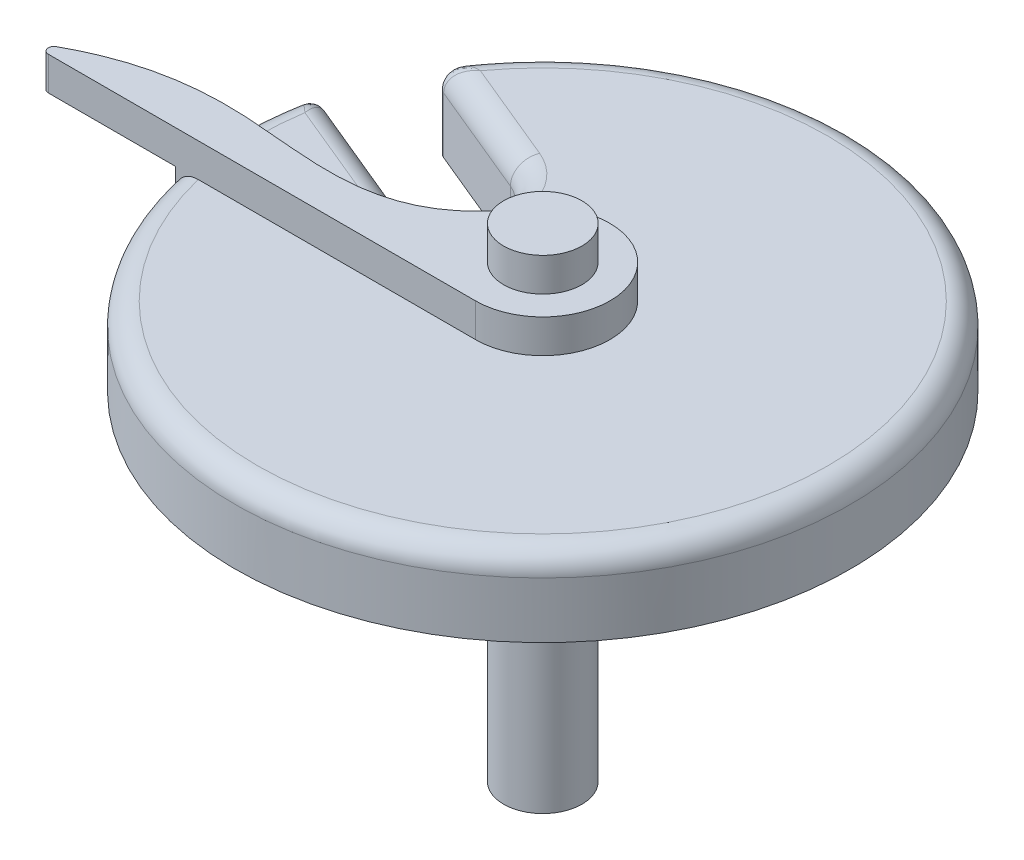
SolidWorks part; units mm, degrees
ref_plane "Front Plane" through (0, 0, 0) normal (0, 0, 1) x (1, 0, 0)
ref_plane "Top Plane" through (0, 0, 0) normal (0, 1, 0) x (1, 0, 0)
ref_plane "Right Plane" through (0, 0, 0) normal (1, 0, 0) x (0, 0, -1)
sketch "Sketch1" plane through (0, 0, 0) normal (0, 1, 0) x (1, 0, 0)
  circle A0 centre (0, 0) radius 27.5
  dimension "D1" = 55
extrude "Boss-Extrude1" add sketch "Sketch1" along normal blind 7
sketch "Sketch2" plane through (0, 7, 0) normal (0, 1, 0) x (1, 0, 0)
  line L0 (0, -6) -> (-40, -6)
  arc A0 (0, -6) -> (-5, 3.3166) centre (0, 0) ccw
  spline S0 degree 3 poles (-5, 3.3166) (-10.2937, -4.6639) (-24.0961, -0.4347) (-35.0297, -2.8344) (-40, -6) knots 0 0 0 0 0.566042 1 1 1 1
  point P7 (0, 0)
  point P8 (0, 0)
  point P9 (-25, -2.3178)
  point P11 (-0.086, 0.4917)
  dimension "D1" = 12
  dimension "D5" = 28.73
  dimension "D2" = 40
  dimension "D3" = 25
  dimension "D4" = 2
  dimension "D6" = 5
extrude "Boss-Extrude2" add sketch "Sketch2" along normal blind 3
fillet "Fillet1" radius 0.5 1 edges at (-40, 8.5, 6)
sketch "Sketch3" plane through (0, 10, 0) normal (0, 1, 0) x (1, 0, 0)
  circle A0 centre (0, 0) radius 3.5
  dimension "D1" = 7
extrude "Boss-Extrude3" add sketch "Sketch3" along normal blind 3 and the other way blind 40.2
sketch "Sketch4" plane through (0, 7, 0) normal (0, 1, 0) x (1, 0, 0)
  line L0 (0, 0) -> (-14.6104, 0) construction
  line L1 (0, 0) -> (-25.4067, 10.5238) construction
  line L2 (-15.3889, 2.0447) -> (-12.3275, 9.4358) construction
  line L3 (-12.3275, 9.4358) -> (-23.6058, 14.1074)
  line L4 (-15.3889, 2.0447) -> (-26.6672, 6.7164)
  arc A0 (-26.8375, -6) -> (-27.4274, -1.9972) centre (0, 0) ccw construction
  arc A1 (-15.3889, 2.0447) -> (-12.3275, 9.4358) centre (-13.8582, 5.7403) ccw
  arc A2 (-23.6058, 14.1074) -> (-26.6672, 6.7164) centre (0, 0) ccw
  dimension "D2" = 4
  dimension "D1" = 22.5
  dimension "D3" = 15
extrude "Cut-Extrude1" cut sketch "Sketch4" against normal through all
fillet "Fillet2" radius 1 2 edges at (-26.6672, 3.5, -6.7164) (-23.6058, 3.5, -14.1074)
fillet "Fillet3" radius 2 7 edges at (-27.4418, 7, -1.7889) (-26.425, 7, -6.223) (-20.4814, 7, -4.1541) (-10.1627, 7, -4.2095) (-17.4199, 7, -11.5451) (-23.0856, 7, -14.285) (27.0494, 7, 4.958)
